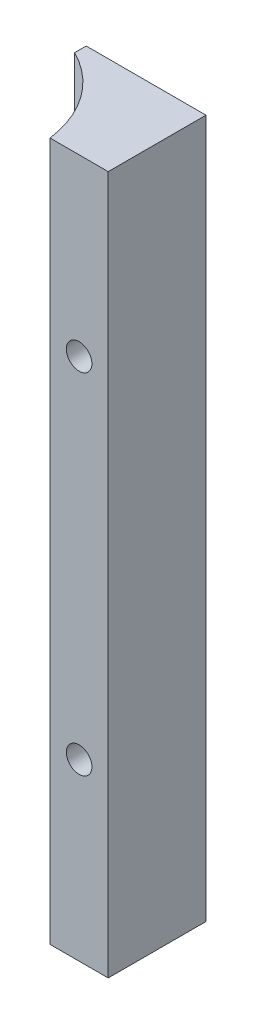
SolidWorks part; units mm, degrees
ref_plane "Front" through (0, 0, 0) normal (0, 0, 1) x (1, 0, 0)
ref_plane "Top" through (0, 0, 0) normal (0, 1, 0) x (1, 0, 0)
ref_plane "Right" through (0, 0, 0) normal (1, 0, 0) x (0, 0, -1)
sketch "Sketch1" plane through (0, 0, 0) normal (0, 1, 0) x (1, 0, 0)
  line L0 (0, 0) -> (0, 8.4)
  line L1 (0, 8.4) -> (-10.2908, 8.4)
  line L2 (-10.2908, 8.4) -> (-10.2908, 7.4)
  line L3 (-5, 0) -> (0, 0)
  arc A0 (-10.2908, 7.4) -> (-5, 0) centre (-14.5687, -1.25) cw
  dimension "D3" = 9.65
  dimension "D1" = 5
  dimension "D2" = 8.4
  dimension "D4" = 1.25
  dimension "D5" = 1
extrude "Boss-Extrude1" add sketch "Sketch1" along normal blind 60
sketch "Sketch2" plane through (0, 0, 0) normal (0, 0, 1) x (1, 0, 0)
  line L0 (-2.5, 60) -> (-2.5, 0) construction
  line L1 (-5, 60) -> (0, 60) construction
  line L2 (-5, 0) -> (0, 0) construction
  point P6 (-2.5, 45)
  point P7 (-2.5, 15)
  dimension "D1" = 15
  dimension "D2" = 15
hole_wizard "Ø2.2 (2.2) Diameter Hole1" positions "3DSketch1" profile "Sketch3" hole size "Ø2.2" standard "ANSI Metric" end condition up to next
sketch3d "3DSketch1"
  point P0 (-2.5, 45, 0)
  point P3 (-2.5, 15, 0)
sketch "Sketch3" plane through (-2.5, 45, 0) normal (1, 0, 0) x (0, -1, 0)
  line L0 (0, 0) -> (0, 8.4)
  line L1 (0, 8.4) -> (1.1, 8.4)
  line L2 (1.1, 8.4) -> (1.1, 0)
  line L5 (1.1, 0) -> (0, 0)
  line L11 (0, -6.35) -> (0, 107.95) construction
  dimension "Thru Hole Dia." = 2.2
  dimension "Thru Hole Depth" = 8.4
